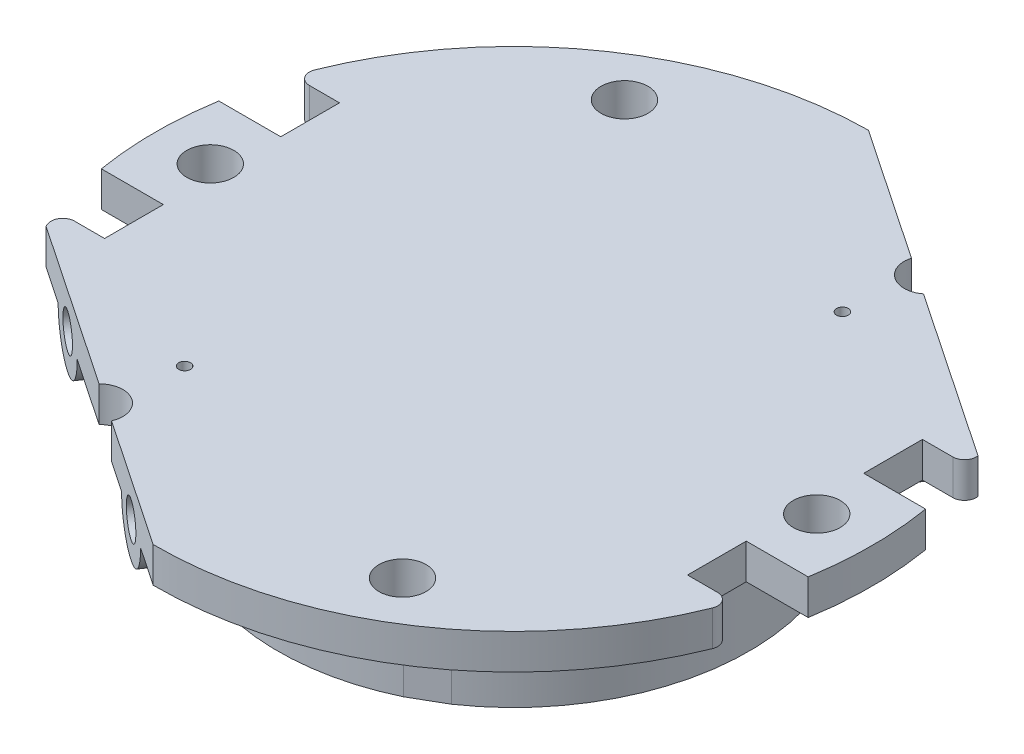
SolidWorks part; units mm, degrees
ref_plane "Alzado" through (0, 0, 0) normal (0, 0, 1) x (1, 0, 0)
ref_plane "Planta" through (0, 0, 0) normal (0, 1, 0) x (1, 0, 0)
ref_plane "Vista lateral" through (0, 0, 0) normal (1, 0, 0) x (0, 0, -1)
sketch "Croquis1" plane through (0, 0, 0) normal (0, 1, 0) x (1, 0, 0)
  circle A0 centre (0, 0) radius 30.5
extrude "Saliente-Extruir1" add sketch "Croquis1" along normal blind 3
sketch "Croquis5" plane through (0, 3, 0) normal (0, 1, 0) x (1, 0, 0)
  line L1 (28.8141, -5) -> (30.0874, -5)
  line L2 (28.8141, 5) -> (30.0874, 5)
  line L3 (-24.8141, 10) -> (-28.8141, 10)
  line L4 (24.8141, -5) -> (24.8141, -10)
  line L5 (-24.8141, -10) -> (-28.8141, -10)
  line L6 (24.8141, -5) -> (28.8141, -5)
  line L7 (24.8141, 5) -> (24.8141, 10)
  line L8 (-24.8141, 5) -> (-28.8141, 5)
  line L9 (-24.8141, 5) -> (-24.8141, 10)
  line L10 (-24.8141, -5) -> (-28.8141, -5)
  line L11 (-24.8141, -5) -> (-24.8141, -10)
  line L12 (24.8141, 5) -> (28.8141, 5)
  line L13 (24.8141, -10) -> (28.8141, -10)
  line L14 (24.8141, 10) -> (28.8141, 10)
  line L15 (-28.8141, 5) -> (-30.0874, 5)
  line L16 (-28.8141, -5) -> (-30.0874, -5)
  line L18 (-24.8141, 0) -> (-12.407, -21.4896)
  line L19 (-12.407, -21.4896) -> (12.407, -21.4896)
  line L20 (12.407, -21.4896) -> (24.8141, 0)
  line L21 (24.8141, 0) -> (12.407, 21.4896)
  line L22 (12.407, 21.4896) -> (-12.407, 21.4896)
  line L23 (-12.407, 21.4896) -> (-24.8141, 0)
  circle A0 centre (0, 0) radius 21.4896 construction
  circle A1 centre (0, 0) radius 30.5 construction
  arc A2 (-28.8141, 10) -> (-30.0874, 5) centre (0, 0) ccw
  arc A4 (-30.0874, -5) -> (-28.8141, -10) centre (0, 0) ccw
  arc A5 (30.0874, -5) -> (28.8141, -10) centre (0, 0) cw
  arc A6 (28.8141, 10) -> (30.0874, 5) centre (0, 0) cw
  circle M2 centre (0, 0) radius 30.5
extrude "Cortar-Extruir3" cut sketch "Croquis5" against normal blind 4 contours L10 L16 L5 L11 M2 | L15 L8 L9 L3 M2 | L14 L7 L12 L2 M2 | L4 L13 L1 L6 M2 region at (27.1844, 3, 7.3876) region at (-27.1844, 3, 7.3876) region at (27.1844, 3, -7.3876) region at (-27.1844, 3, -7.3876)
sketch "Croquis7" plane through (0, 3, 0) normal (0, 1, 0) x (1, 0, 0)
  line L2 (25.8141, 0) -> (12.907, 22.3556)
  line L3 (12.907, 22.3556) -> (-12.907, 22.3556)
  line L4 (-12.907, 22.3556) -> (-25.8141, 0)
  line L5 (-25.8141, 0) -> (-12.907, -22.3556)
  line L6 (-12.907, -22.3556) -> (12.907, -22.3556)
  line L7 (12.907, -22.3556) -> (25.8141, 0)
  circle A0 centre (25.8141, 0) radius 2
  circle A4 centre (-25.8141, 0) radius 2
  circle A5 centre (0, 0) radius 22.3556 construction
  circle A6 centre (12.907, 22.3556) radius 2
  circle A7 centre (-12.907, -22.3556) radius 2
  circle A8 centre (-12.907, 22.3556) radius 2
  circle A9 centre (12.907, -22.3556) radius 2
extrude "Cortar-Extruir4" cut sketch "Croquis7" against normal blind 10 contours A8 L4 L3 | A4 L4 L5 | A4 L5 L4 | A8 L3 L4 | L2 A6 L3 | L3 A6 L2 | L7 A0 L2 | L2 A0 L7 | A7 L5 L6 | A7 L6 L5 | L6 A9 L7 | L7 A9 L6 | A4 region at (24.7114, 3, 0) region at (26.3654, 3, 0) region at (12.3557, 3, -21.4007) region at (13.1827, 3, -22.8331) region at (13.1827, 3, 22.8331) region at (12.3557, 3, 21.4007) region at (-12.3557, 3, -21.4007) region at (-13.1827, 3, -22.8331) region at (-13.1827, 3, 22.8331) region at (-12.3557, 3, 21.4007) region at (-24.7114, 3, 0) region at (-26.3654, 3, 0)
sketch "Croquis8" plane through (0, 3, 0) normal (0, 1, 0) x (1, 0, 0)
  line L0 (0, 0) -> (12, 0)
  line L1 (12, 0) -> (12, 16)
  line L2 (0, 0) -> (-12, 0)
  line L3 (-12, 0) -> (-12, -16)
  circle A0 centre (12, 16) radius 0.5
  circle A1 centre (-12, -16) radius 0.5
extrude "Cortar-Extruir5" cut sketch "Croquis8" against normal blind 3 contours A1 | A0 region at (11.6564, 3, -16.3436) region at (-11.6564, 3, 15.6564)
sketch "Croquis9" plane through (0, 3, 0) normal (0, 1, 0) x (1, 0, 0)
  line L2 (-10, 17.3205) -> (-8.701, 18.0705)
  line L5 (25.6318, 16.5306) -> (27.1318, 13.9325)
  line L6 (-10, 17.3205) -> (-11.299, 16.5705)
  line L8 (10, -17.3205) -> (8.701, -18.0705)
  line L9 (10, -17.3205) -> (11.299, -16.5705)
  circle A0 centre (0, 0) radius 20.0562
  circle A1 centre (-12, -16) radius 3
  circle A2 centre (12, 16) radius 3
extrude "Saliente-Extruir2" add sketch "Croquis9" against normal blind 13 contours L2 L6 | L8 L9 region at (0, 3, 0)
sketch "Croquis11" plane through (14.0495, 0, -20.8293) normal (0.5592, 0, -0.829) x (-0.829, 0, -0.5592)
  line L1 (17.2916, 0) -> (-17.2916, 0)
  line L2 (17.2916, 0) -> (17.2916, 3)
  line L3 (17.2916, 3) -> (-17.2916, 3)
  line L4 (-17.2916, 0) -> (-17.2916, 3)
extrude "Saliente-Extruir3" add sketch "Croquis11" along normal blind 6
sketch "Croquis12" plane through (0, 3, 0) normal (0, 1, 0) x (1, 0, 0)
  circle A0 centre (12.907, 22.3556) radius 2
extrude "Cortar-Extruir7" cut sketch "Croquis12" against normal blind 3
sketch "Croquis13" plane through (17.4047, 0, -25.8035) normal (0.5592, 0, -0.829) x (-0.829, 0, -0.5592)
  line L0 (-17.2916, 0) -> (17.2916, 0)
  line L1 (17.2916, 3) -> (-17.2916, 3)
  line L2 (17.2916, 3) -> (-17.2916, 3) construction
  line L3 (17.2916, 0) -> (17.2916, 3) construction
  circle A1 centre (10, 0) radius 3
  circle A2 centre (-10, 0) radius 3
  circle A3 centre (10, 0) radius 1.5
  circle A5 centre (-10, 0) radius 1.5
  line M4 (-17.2916, 0) -> (17.2916, 0)
extrude "Saliente-Extruir4" add sketch "Croquis13" against normal blind 20 contours A3 L0 A1 | A3 L0 A1 | A5 L0 A2 | A5 L0 A2 | A5 M4 | A3 M4 region at (25.6951, 1.5671, -20.2116) region at (25.6951, -0.6366, -20.2116) region at (23.8297, -0.0671, -21.4698) region at (10.8337, 2.0739, -30.2358) region at (10.9797, -0.0671, -30.1373) region at (9.1143, -0.6366, -31.3955)
sketch "Croquis14" plane through (17.4047, 0, -25.8035) normal (0.5592, 0, -0.829) x (-0.829, 0, -0.5592)
  circle A0 centre (-10, 0) radius 1.5
  circle A1 centre (10, 0) radius 1.5
extrude "Cortar-Extruir8" cut sketch "Croquis14" against normal blind 6
sketch "Croquis15" plane through (0, 3, 0) normal (0, 1, 0) x (1, 0, 0)
  line L0 (28.3849, 11.16) -> (-0.2859, 30.4987)
  line L1 (28.3849, 11.16) -> (0.1409, -30.7136)
  line L2 (-0.2859, 30.4987) -> (-28.5299, -11.3749)
  line L3 (0.1409, -30.7136) -> (-28.5299, -11.3749)
  circle A0 centre (-0.2859, 0) radius 30.7165
  arc M12 (-28.8141, -10) -> (28.8141, -10) centre (0, 0) ccw
  circle M28 centre (-12.907, -22.3556) radius 2
extrude "Cortar-Extruir9" cut sketch "Croquis15" against normal blind 3 contours L3 M12 M28 region at (-15.494, 3, 22.7434)
sketch "Croquis16" plane through (-14.1945, 0, 21.0442) normal (-0.5592, 0, 0.829) x (0.829, 0, 0.5592)
  line L0 (-16.9088, 0) -> (-16.9088, 3)
  line L1 (-16.9088, 0) -> (16.78, 0)
  line L2 (-16.9088, 3) -> (16.78, 3)
  line L3 (16.78, 0) -> (16.78, 3)
extrude "Saliente-Extruir5" add sketch "Croquis16" along normal blind 6
sketch "Croquis17" plane through (0, 3, 0) normal (0, 1, 0) x (1, 0, 0)
  circle A0 centre (-12.907, -22.3556) radius 2
extrude "Cortar-Extruir10" cut sketch "Croquis17" against normal blind 3
sketch "Croquis18" plane through (-17.5497, 0, 26.0185) normal (-0.5592, 0, 0.829) x (0.829, 0, 0.5592)
  line L2 (-16.9088, 0) -> (16.78, 0) construction
  circle A0 centre (9.9356, 0) radius 3
  circle A1 centre (-10.0644, 0) radius 3
extrude "Saliente-Extruir6" add sketch "Croquis18" against normal blind 25
sketch "Croquis19" plane through (-17.5497, 0, 26.0185) normal (-0.5592, 0, 0.829) x (0.829, 0, 0.5592)
  circle A0 centre (-10.0644, 0) radius 1.5
  circle A1 centre (9.9356, 0) radius 1.5
extrude "Cortar-Extruir11" cut sketch "Croquis19" against normal blind 5
sketch "Croquis20" plane through (17.4047, 0, -25.8035) normal (0.5592, 0, -0.829) x (-0.829, 0, -0.5592)
  line L0 (17.2916, 3) -> (17.2916, 0)
  line L1 (17.2916, 0) -> (13, 0)
  line L2 (-7, 0) -> (7, 0) construction
  line L3 (7, 0) -> (-7, 0)
  line L4 (-13, 0) -> (-17.2916, 0)
  line L5 (-17.2916, 0) -> (-17.2916, 3)
  line L6 (-17.2916, 3) -> (17.2916, 3)
  arc A0 (13, 0) -> (7, 0) centre (10, 0) cw
  arc A1 (7, 0) -> (13, 0) centre (10, 0) ccw construction
  arc A2 (-7, 0) -> (-13, 0) centre (-10, 0) cw
extrude "Cortar-Extruir12" cut sketch "Croquis20" against normal blind 6
sketch "Croquis21" plane through (-17.5497, 0, 26.0185) normal (-0.5592, 0, 0.829) x (0.829, 0, 0.5592)
  line L0 (-13.0644, 0) -> (-16.9088, 0)
  line L1 (-16.9088, 0) -> (-16.9088, 3)
  line L2 (-16.9088, 3) -> (16.78, 3)
  line L3 (16.78, 3) -> (16.78, 0)
  line L4 (16.78, 0) -> (12.9356, 0)
  line L5 (6.9356, 0) -> (-7.0644, 0)
  arc A0 (-13.0644, 0) -> (-7.0644, 0) centre (-10.0644, 0) ccw
  arc A1 (6.9356, 0) -> (12.9356, 0) centre (9.9356, 0) ccw
extrude "Cortar-Extruir13" cut sketch "Croquis21" against normal blind 6
sketch "Croquis22" plane through (-14.1945, 0, 21.0442) normal (-0.5592, 0, 0.829) x (0.829, 0, 0.5592)
  circle A0 centre (-10.0644, 0) radius 1.5
  circle A1 centre (9.9356, 0) radius 1.5
extrude "Cortar-Extruir14" cut sketch "Croquis22" against normal blind 6
sketch "Croquis23" plane through (14.0495, 0, -20.8293) normal (0.5592, 0, -0.829) x (-0.829, 0, -0.5592)
  circle A0 centre (-10, 0) radius 1.5
  circle A1 centre (10, 0) radius 1.5
extrude "Cortar-Extruir15" cut sketch "Croquis23" against normal blind 6
fillet "Redondeo1" radius 1 4 edges at (-28.8141, 1.5, -10) (-28.8141, 1.5, 10) (28.8141, 1.5, 10) (28.8141, 1.5, -10)
